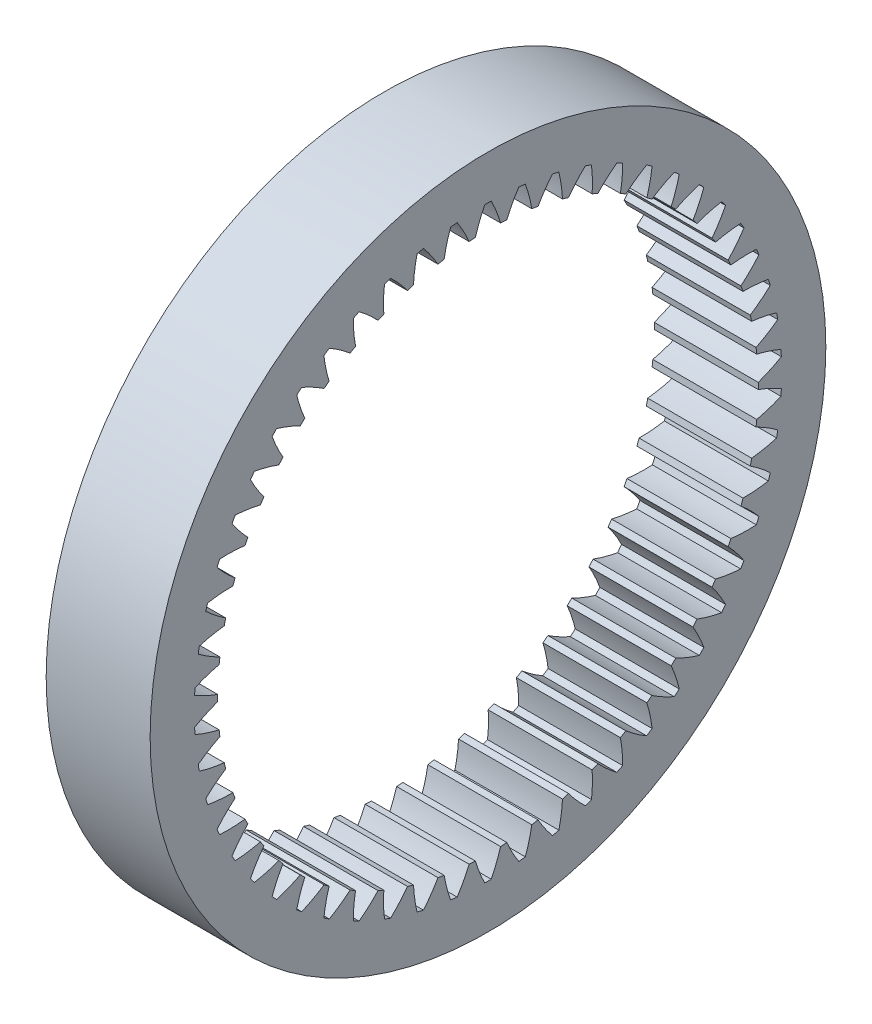
SolidWorks part; units mm, degrees
ref_plane "Plane1" through (0, 0, 0) normal (0, 0, 1) x (1, 0, 0)
ref_plane "Plane2" through (0, 0, 0) normal (0, 1, 0) x (1, 0, 0)
ref_plane "Plane3" through (0, 0, 0) normal (1, 0, 0) x (0, 0, -1)
sketch "HoldingSke" plane through (0, 0, 0) normal (0, 1, 0) x (1, 0, 0)
  line L0 (0, 0) -> (0.2939, -0.4045)
  line L1 (-15, 0) -> (100, 0) construction
  line L2 (0, 0) -> (-2.1039, 2.3779)
  line L3 (0, 0) -> (-11.863, 4.5341)
  line L4 (0, 0) -> (5.0761, 6.9867)
  line L5 (0, 0) -> (-23.7986, -8.8762)
  line L6 (0, 0) -> (-10.5278, -7.1032)
  line L7 (-2.1039, 2.3779) -> (3.3635, 27.1825)
  line L8 (-76.2, 4.3779) -> (-54.61, 4.3779)
  line L9 (-71.009, 38.7566) -> (-53.1078, 45.2721)
  line L10 (-76.2, 71.12) -> (104.1128, 71.12)
  line L11 (0, 0) -> (-20, 0)
  line L12 (-76.2, 101.6) -> (-76.133, 101.6)
  line L13 (24.9733, 27.94) -> (52.9518, 28.4284)
  line L14 (24.9733, 27.94) -> (24.9743, 27.94)
  line L15 (24.9733, 27.94) -> (100.4006, 29.5858)
  circle A0 centre (0, 0) radius 65
  circle A1 centre (0, 0) radius 12.7
  circle A2 centre (0, 0) radius 12.7
  dimension "Num_teeth" = 54
  dimension "Pitch_radius" = 180.3128
  dimension "Width" = 20
  dimension "Diameter" = 130
sketch "BasProSke" plane through (0, 0, 0) normal (0, 1, 0) x (1, 0, 0)
  line L0 (-10, 0) -> (60, 0) construction
  line L1 (0, 52) -> (0, 65)
  line L2 (0, 52) -> (20, 52)
  line L3 (20, 52) -> (20, 65)
  line L4 (20, 65) -> (0, 65)
  dimension "Thickness" = 20
  dimension "Diameter" = 130
revolve "Base-Revolve" add sketch "BasProSke" angle 360 about L0
sketch "TooCutSke" plane through (0, 0, 0) normal (1, 0, 0) x (0, 0, -1)
  line L3 (1.7381, 53.972) -> (1.7381, 53.6633) construction
  line L4 (0, 0) -> (0, 59.563) construction
  line L5 (0, 0) -> (-3.9729, 68.2119) construction
  line L6 (-23.4998, 44.3778) -> (35.1234, 47.7922) construction
  circle A0 centre (0, 0) radius 54 construction
  circle A1 centre (0, 0) radius 56.501 construction
  circle A2 centre (0, 0) radius 45.6691 construction
  circle A3 centre (0, 0) radius 51.9746 construction
  arc A4 (2.426, 51.918) -> (0.6272, 56.4975) centre (-23.4998, 44.3778) ccw
  arc A5 (2.426, 51.918) -> (-2.426, 51.918) centre (0, 0) ccw
  arc A6 (0.6272, 56.4975) -> (-0.6272, 56.4975) centre (0, 0) ccw
  arc A7 (-0.6272, 56.4975) -> (-2.426, 51.918) centre (23.4998, 44.3778) ccw
extrude "ToothCut" cut sketch "TooCutSke" along normal through all
fillet "Breaks" [suppressed] radius 0.2
fillet "RootFillets" [suppressed] radius 0.501
pattern_circular "TeethCuts" count 54 every 6.667 about axis through (-10, 0, 0) along (1, 0, 0) of "RootFillets", "Breaks", "ToothCut"
equation "' \"Module@HoldingSke\" = 6.35"
equation "' \"Num_teeth@HoldingSke\" = 24"
equation "' \"Ap@HoldingSke\" =  14.5"
equation "' \"Ap@HoldingSke\" = 14.5"
equation "' \"Width@HoldingSke\" = 12"
equation "' \"Diameter@HoldingSke\" = 8 * 25.4"
equation "' \"Show_teeth@HoldingSke\" = 100"
equation "' \"Backlash@HoldingSke\" = 0.009 * 25.4"
equation "' \"Addendum_fac@HoldingSke\" = 1.0"
equation "' \"Dedendum_fac@HoldingSke\" = 1.25"
equation "' \"Dedendum_add@HoldingSke\" = 0.00005 * 25.4"
equation "' \"Clearance_fac@HoldingSke\" = 0.25"
equation "\"Pitch@HoldingSke\" = 1 / \"Module@HoldingSke\" "
equation "\"Overcut_dia@TooCutSke\" = (\"Num_teeth@HoldingSke\" - 2 * \"Addendum_fac@HoldingSke\") / \"Pitch@HoldingSke\" - 0.002 * 25.4"
equation "\"Pitch_dia@TooCutSke\" = \"Num_teeth@HoldingSke\" / \"Pitch@HoldingSke\""
equation "\"Base_dia@TooCutSke\" = \"Num_teeth@HoldingSke\" / \"Pitch@HoldingSke\" * cos((\"Ap@HoldingSke\"  * 3.14159265 / 180)) * 0.90"
equation "\"Root_dia@TooCutSke\" = \"Num_teeth@HoldingSke\"  / \"Pitch@HoldingSke\" + 2 *  \"Dedendum_fac@HoldingSke\"/ \"Pitch@HoldingSke\" + \"Dedendum_add@HoldingSke\" * 2"
equation "\"Half_ang@TooCutSke\" = 180 / \"Num_teeth@HoldingSke\""
equation "\"Half_CT@TooCutSke\" = \"Num_teeth@HoldingSke\" / \"Pitch@HoldingSke\" * sin((3.14159265 / 2 / \"Num_teeth@HoldingSke\")) / 2 + 10 * \"Backlash@HoldingSke\" / 4"
equation "\"Flank_rad@TooCutSke\" = \"Num_teeth@HoldingSke\" / \"Pitch@HoldingSke\" / 4"
equation "\"Radius@RootFillets\"= \"Clearance_fac@HoldingSke\" / \"Pitch@HoldingSke\" + \"Dedendum_add@HoldingSke\""
equation "\"Break_rad@Breaks\" = 0.02 / \"Pitch@HoldingSke\" * 5"
equation "\"Num_teeth@TeethCuts\" = int( \"Show_teeth@HoldingSke\" ) + 1"
equation "\"Num_teeth@TeethCuts\" = ((sgn( \"Num_teeth@TeethCuts\" - \"Num_teeth@HoldingSke\" )-1)*( \"Num_teeth@TeethCuts\" - \"Num_teeth@HoldingSke\" ))/-2+ \"Num_teeth@HoldingSke\""
equation "\"Num_teeth@TeethCuts\" = ((sgn( \"Num_teeth@TeethCuts\" - 2.0)+1)*( \"Num_teeth@TeethCuts\" - 2.0))/2 +2.0"
equation "\"Angle@TeethCuts\" = 360.0 / \"Num_teeth@HoldingSke\""
equation "\"Diameter@BasProSke\" = \"Num_teeth@HoldingSke\"  / \"Pitch@HoldingSke\" + 2 *  \"Dedendum_fac@HoldingSke\"/ \"Pitch@HoldingSke\" + \"Dedendum_add@HoldingSke\" * 2 + 0.002 * 25.4"
equation "\"Diameter@BasProSke\" = ((sgn( \"Diameter@BasProSke\"  - \"Diameter@HoldingSke\" )+1)*( \"Diameter@BasProSke\"  - \"Diameter@HoldingSke\" ))/2 + \"Diameter@HoldingSke\""
equation "\"Inside_diameter@BasProSke\" =  (\"Num_teeth@HoldingSke\" - 2 * \"Addendum_fac@HoldingSke\") / \"Pitch@HoldingSke\" "
equation "\"Thickness@BasProSke\"  = \"Width@HoldingSke\""
